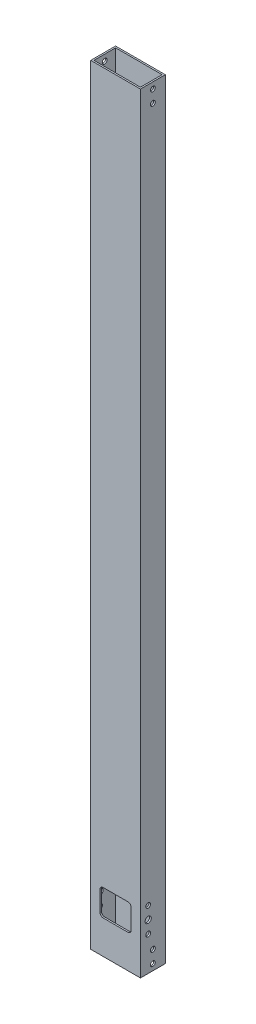
SolidWorks part; units mm, degrees
ref_plane "Front Plane" through (0, 0, 0) normal (0, 0, 1) x (1, 0, 0)
ref_plane "Top Plane" through (0, 0, 0) normal (0, 1, 0) x (1, 0, 0)
ref_plane "Right Plane" through (0, 0, 0) normal (1, 0, 0) x (0, 0, -1)
sketch "Sketch1" plane through (0, 0, 0) normal (0, 0, 1) x (1, 0, 0)
  line L1 (-25.4, -393.7) -> (25.4, -393.7)
  line L2 (-25.4, -393.7) -> (-25.4, 393.7)
  line L3 (-25.4, 393.7) -> (25.4, 393.7)
  line L4 (25.4, -393.7) -> (25.4, 393.7)
  line L5 (-25.4, -393.7) -> (25.4, 393.7) construction
  line L6 (-25.4, 393.7) -> (25.4, -393.7) construction
  point P0 (0, 0)
  dimension "D1" = 50.8
  dimension "D2" = 787.4
extrude "Boss-Extrude1" add sketch "Sketch1" along normal mid plane 25.4
shell "Shell1" thickness 1.5875 removed face at (0, -393.7, 0) removed face at (0, 393.7, 0)
sketch "Sketch3" plane through (0, 0, 0) normal (1, 0, 0) x (0, 0, -1)
  line L0 (-12.7, -393.7) -> (12.7, -393.7) construction
  circle A0 centre (0, -387.35) radius 2.4892
  circle A1 centre (0, -374.65) radius 2.4892
  point P6 (0, -393.7)
  dimension "D1" = 4.9784
  dimension "D2" = 6.35
  dimension "D3" = 12.7
extrude "Cut-Extrude1" cut sketch "Sketch3" against normal through all both and the other way through all
sketch "Sketch4" plane through (0, 0, 0) normal (1, 0, 0) x (0, 0, -1)
  line L4 (-12.7, -393.7) -> (12.7, -393.7) construction
  line L5 (-12.7, 393.7) -> (-12.7, -393.7) construction
  circle A3 centre (-4.7625, -346.075) radius 3.175
  circle A4 centre (-4.7625, -333.375) radius 2.4892
  circle A5 centre (-4.7625, -358.775) radius 2.4892
  dimension "D7" = 6.35
  dimension "D8" = 4.9784
  dimension "D9" = 12.7
  dimension "D10" = 12.7
  dimension "D11" = 47.625
  dimension "D12" = 7.9375
extrude "Cut-Extrude2" cut sketch "Sketch4" against normal through all both and the other way through all
mirror "Mirror1" about plane through (0, 0, 0) normal (0, 1, 0) of "Cut-Extrude1"
sketch "Sketch5" plane through (0, 0, 0) normal (0, 0, 1) x (1, 0, 0)
  line L0 (-25.4, -393.7) -> (25.4, -393.7) construction
  line L1 (-15.875, -332.5812) -> (15.875, -332.5812)
  line L2 (-15.875, -332.5812) -> (-15.875, -359.5687)
  line L3 (-15.875, -359.5687) -> (15.875, -359.5687)
  line L4 (15.875, -332.5812) -> (15.875, -359.5687)
  point P4 (0, -359.5687)
  point P7 (0, -393.7)
  point P8 (15.875, -346.075)
  dimension "D1" = 31.75
  dimension "D2" = 26.9875
  dimension "D3" = 47.625
extrude "Cut-Extrude3" cut sketch "Sketch5" along normal through all
fillet "Fillet1" radius 3.175 4 edges at (-15.875, -359.5687, 11.9062) (15.875, -359.5687, 11.9062) (-15.875, -332.5812, 11.9062) (15.875, -332.5812, 11.9062)
